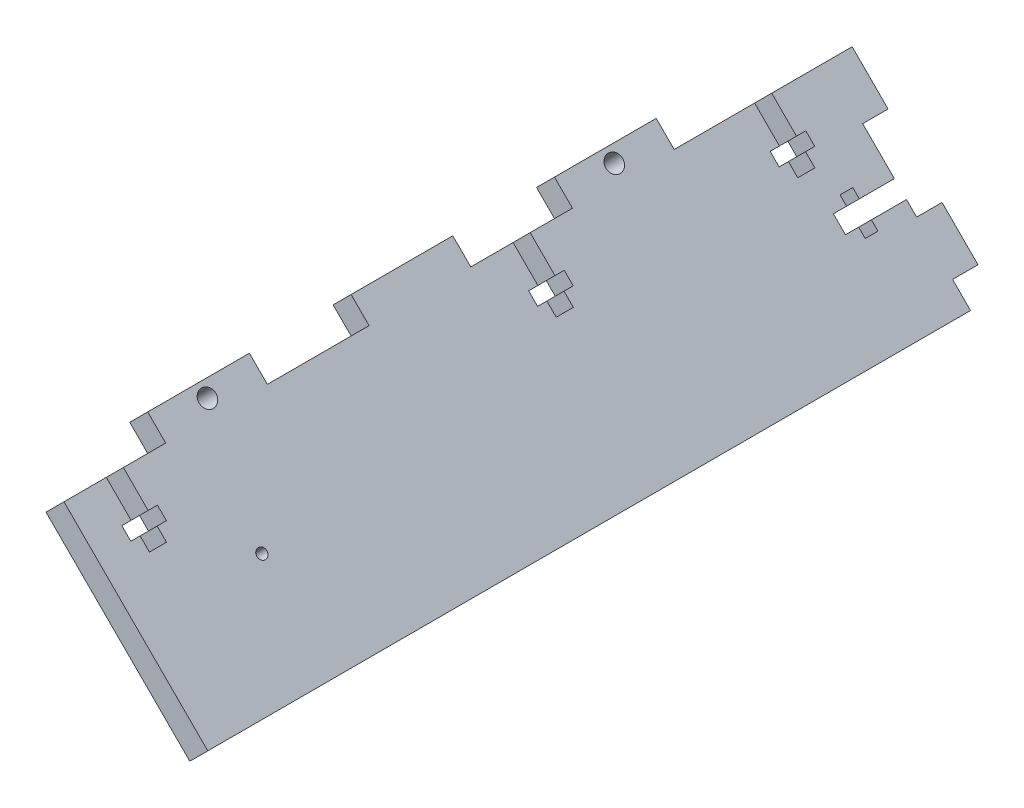
SolidWorks part; units mm, degrees
ref_plane "Front Plane" through (0, 0, 0) normal (0, 0, 1) x (1, 0, 0)
ref_plane "Top Plane" through (0, 0, 0) normal (0, 1, 0) x (1, 0, 0)
ref_plane "Right Plane" through (0, 0, 0) normal (1, 0, 0) x (0, 0, -1)
sketch "Sketch1" plane through (0, 0, 0) normal (0, 0, 1) x (1, 0, 0)
  line L0 (-105.5101, 43.1479) -> (-54.0999, -8.2622) construction
  line L1 (-19.5508, -47.3014) -> (-62.6554, -4.1968) construction
  line L2 (-58.1653, 0.2933) -> (-15.0607, -42.8113) construction
  line L3 (-73.6381, 43.6049) -> (-37.7171, 7.6839)
  line L4 (-73.6381, 43.6049) -> (-69.148, 48.095)
  line L5 (-37.7171, 7.6839) -> (-33.2269, 12.174)
  line L6 (-69.148, 48.095) -> (-33.2269, 12.174)
  line L7 (-70.046, -24.645) -> (-105.967, 11.276) construction
  line L8 (-74.5361, -29.1352) -> (-70.046, -24.645) construction
extrude "Boss-Extrude1" add sketch "Sketch1" along normal up to surface (190.5 mm away)
sketch "Sketch2" plane through (-58.6215, 58.6215, 0) normal (-0.7071, 0.7071, 0) x (0, 0, 1)
  line L0 (190.5, -14.8867) -> (0, -14.8867) construction
  line L1 (165.1, -14.8867) -> (139.7, -14.8867)
  line L2 (165.1, -14.8867) -> (165.1, -21.2367)
  line L3 (165.1, -21.2367) -> (139.7, -21.2367)
  line L4 (139.7, -14.8867) -> (139.7, -21.2367)
  line L5 (190.5, -21.2367) -> (0, -21.2367) construction
  dimension "D1" = 25.4
  dimension "D2" = 25.4
extrude "Boss-Extrude2" add sketch "Sketch2" along normal blind 6.35
pattern_linear "LPattern1" count 3 spacing 50.8 along (0, 0, -1) of "Boss-Extrude2"
sketch "Sketch3" plane through (0, 0, 0) normal (0, 0, -1) x (-1, 0, 0)
  line L0 (73.6381, 43.6049) -> (64.6578, 34.6246)
  line L1 (73.6381, 43.6049) -> (37.7171, 7.6839) construction
  line L2 (64.6578, 34.6246) -> (60.1677, 39.1148)
  line L3 (33.2269, 12.174) -> (69.148, 48.095) construction
  line L4 (60.1677, 39.1148) -> (69.148, 48.095)
  line L5 (69.148, 48.095) -> (73.6381, 43.6049)
  dimension "D1" = 12.7
extrude "Boss-Extrude3" add sketch "Sketch3" along normal blind 6.35
pattern_linear "LPattern2" count 2 spacing 31.75 along (0.7071, -0.7071, 0) of "Boss-Extrude3"
sketch "Sketch4" plane through (-10.5265, -10.5265, 0) normal (0.7071, 0.7071, 0) x (0, 0, -1)
  circle A0 centre (-159.0375, 57.5033) radius 1.25
  dimension "D1" = 2.5
extrude "Cut-Extrude1" cut sketch "Sketch4" against normal through all
sketch "Sketch5" plane through (-10.5265, -10.5265, 0) normal (0.7071, 0.7071, 0) x (0, 0, -1)
  line L0 (-177.8, 82.9033) -> (-177.8, 68.4326) construction
  line L1 (-190.5, 82.9033) -> (-165.1, 82.9033) construction
  line L2 (-76.2, 82.9033) -> (-76.2, 62.5112) construction
  line L3 (-88.9, 82.9033) -> (-63.5, 82.9033) construction
  line L4 (-15.875, 82.9033) -> (-15.875, 66.2052) construction
  line L5 (-38.1, 82.9033) -> (6.35, 82.9033) construction
  line L6 (-38.1412, 82.9033) -> (0, 82.9033) construction
  line B0 (-175.6664, 82.9033) -> (-179.9336, 82.9033)
  line B1 (-179.9336, 70.9653) -> (-182.245, 70.9653)
  line B2 (-182.245, 70.9653) -> (-182.245, 74.1403)
  line B3 (-182.245, 74.1403) -> (-179.9336, 74.1403)
  line B4 (-179.9336, 74.1403) -> (-179.9336, 82.9033)
  line B5 (-179.9336, 70.9653) -> (-179.9336, 67.6633)
  line B6 (-179.9336, 67.6633) -> (-175.6664, 67.6633)
  line B7 (-175.6664, 70.9653) -> (-175.6664, 67.6633)
  line B8 (-175.6664, 74.1403) -> (-175.6664, 82.9033)
  line B9 (-173.355, 74.1403) -> (-175.6664, 74.1403)
  line B10 (-173.355, 70.9653) -> (-173.355, 74.1403)
  line B11 (-175.6664, 70.9653) -> (-173.355, 70.9653)
  line B12 (-74.0664, 82.9033) -> (-78.3336, 82.9033)
  line B13 (-78.3336, 70.9653) -> (-80.645, 70.9653)
  line B14 (-80.645, 70.9653) -> (-80.645, 74.1403)
  line B15 (-80.645, 74.1403) -> (-78.3336, 74.1403)
  line B16 (-78.3336, 74.1403) -> (-78.3336, 82.9033)
  line B17 (-78.3336, 70.9653) -> (-78.3336, 67.6633)
  line B18 (-78.3336, 67.6633) -> (-74.0664, 67.6633)
  line B19 (-74.0664, 70.9653) -> (-74.0664, 67.6633)
  line B20 (-74.0664, 74.1403) -> (-74.0664, 82.9033)
  line B21 (-71.755, 74.1403) -> (-74.0664, 74.1403)
  line B22 (-71.755, 70.9653) -> (-71.755, 74.1403)
  line B23 (-74.0664, 70.9653) -> (-71.755, 70.9653)
  line B24 (-13.7414, 82.9033) -> (-18.0086, 82.9033)
  line B25 (-18.0086, 70.9653) -> (-20.32, 70.9653)
  line B26 (-20.32, 70.9653) -> (-20.32, 74.1403)
  line B27 (-20.32, 74.1403) -> (-18.0086, 74.1403)
  line B28 (-18.0086, 74.1403) -> (-18.0086, 82.9033)
  line B29 (-18.0086, 70.9653) -> (-18.0086, 67.6633)
  line B30 (-18.0086, 67.6633) -> (-13.7414, 67.6633)
  line B31 (-13.7414, 70.9653) -> (-13.7414, 67.6633)
  line B32 (-13.7414, 74.1403) -> (-13.7414, 82.9033)
  line B33 (-11.43, 74.1403) -> (-13.7414, 74.1403)
  line B34 (-11.43, 70.9653) -> (-11.43, 74.1403)
  line B35 (-13.7414, 70.9653) -> (-11.43, 70.9653)
sketch_block_instance "TSlot-1"
sketch_block "TSlot" parameters "D1"=3.302, "D2"=3.175
sketch_block_instance "TSlot-2"
sketch_block_instance "TSlot-3"
extrude "Cut-Extrude2" cut sketch "Sketch5" against normal through all
sketch "Sketch6" plane through (-15.0166, -15.0166, 0) normal (-0.7071, -0.7071, 0) x (0, 0, 1)
  line L0 (150.287, 89.2533) -> (154.5542, 82.9033) construction
  line L1 (139.7, 89.2533) -> (165.1, 89.2533) construction
  line L2 (150.287, 89.2533) -> (150.287, 82.9033) construction
  line L3 (154.5542, 89.2533) -> (150.287, 82.9033) construction
  line L4 (154.5542, 82.9033) -> (154.5542, 89.2533) construction
  line L5 (48.687, 89.2533) -> (52.9542, 82.9033) construction
  line L6 (38.1, 89.2533) -> (63.5, 89.2533) construction
  line L7 (48.687, 89.2533) -> (48.687, 82.9033) construction
  line L8 (52.9542, 89.2533) -> (48.687, 82.9033) construction
  line L9 (52.9542, 82.9033) -> (52.9542, 89.2533) construction
  circle A0 centre (152.4206, 86.0783) radius 2.0955
  circle A1 centre (50.8206, 86.0783) radius 2.0955
  dimension "D1" = 4.191
extrude "Cut-Extrude3" cut sketch "Sketch6" against normal through all
sketch "Sketch7" plane through (-10.5265, -10.5265, 0) normal (0.7071, 0.7071, 0) x (0.7071, -0.7071, 0)
  line L0 (-56.8683, 0) -> (-56.8683, -24.4742) construction
  line L1 (-51.1533, 0) -> (-70.2033, 0) construction
  line L4 (-67.6633, -18.0086) -> (-67.6633, -13.7414) construction
  line B0 (-54.7347, 0) -> (-59.0019, 0)
  line B1 (-59.0019, -11.938) -> (-61.3133, -11.938)
  line B2 (-61.3133, -11.938) -> (-61.3133, -8.763)
  line B3 (-61.3133, -8.763) -> (-59.0019, -8.763)
  line B4 (-59.0019, -8.763) -> (-59.0019, 0)
  line B5 (-59.0019, -11.938) -> (-59.0019, -15.24)
  line B6 (-59.0019, -15.24) -> (-54.7347, -15.24)
  line B7 (-54.7347, -11.938) -> (-54.7347, -15.24)
  line B8 (-54.7347, -8.763) -> (-54.7347, 0)
  line B9 (-52.4233, -8.763) -> (-54.7347, -8.763)
  line B10 (-52.4233, -11.938) -> (-52.4233, -8.763)
  line B11 (-54.7347, -11.938) -> (-52.4233, -11.938)
  dimension "D1" = 6.35
sketch_block_instance "TSlot-4"
extrude "Cut-Extrude4" cut sketch "Sketch7" against normal through all
